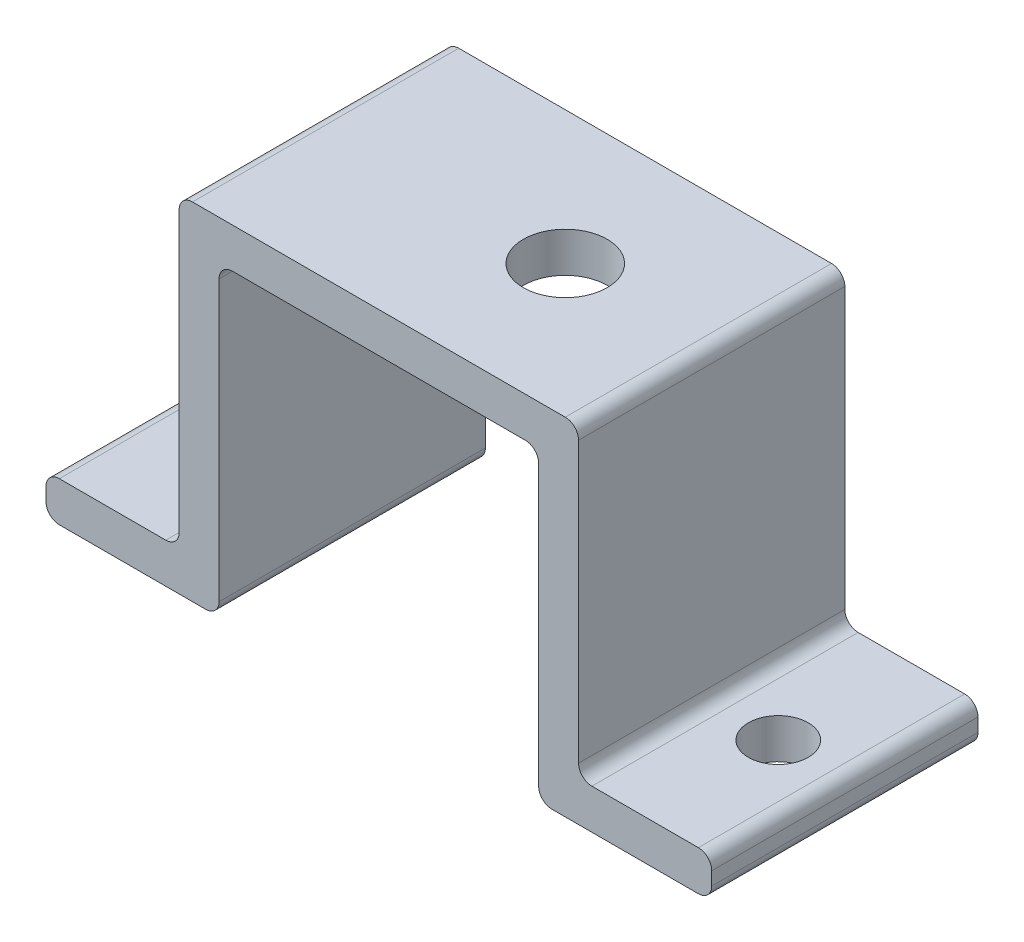
SolidWorks part; units mm, degrees
ref_plane "Front Plane" through (0, 0, 0) normal (0, 0, 1) x (1, 0, 0)
ref_plane "Top Plane" through (0, 0, 0) normal (0, 1, 0) x (1, 0, 0)
ref_plane "Right Plane" through (0, 0, 0) normal (1, 0, 0) x (0, 0, -1)
sketch "Sketch2" plane through (0, 0, 0) normal (0, 0, 1) x (1, 0, 0)
  line L1 (-12, 0) -> (12, 0)
  line L2 (-15, -20) -> (-15, 3)
  line L3 (-15, 3) -> (15, 3)
  line L4 (15, -20) -> (15, 3)
  line L15 (-15, -20) -> (-25, -20)
  line L16 (-12, 0) -> (-12, -23)
  line L17 (-12, -23) -> (-25, -23)
  line L18 (-25, -20) -> (-25, -23)
  line L19 (15, -20) -> (25, -20)
  line L20 (12, 0) -> (12, -23)
  line L21 (12, -23) -> (25, -23)
  line L22 (25, -20) -> (25, -23)
  point P0 (0, 0)
  point P7 (-20, -6.3216)
  point P8 (-27.8471, 12.8275)
  point P10 (-35, -6.8038)
  point P11 (-24.2653, -8.6636)
  point P18 (-86.5056, -58.0001)
  point P19 (0, 0)
  point P20 (-61.8668, 28.3256)
  point P21 (20, -8.2503)
  point P22 (-20, -8.6636)
  point P23 (-12, -11.5)
  point P24 (-25.023, -13.692)
  point P25 (0, 0)
  point P26 (0, 0)
  point P27 (-35, -15.1385)
  point P28 (-29, 3)
  point P29 (-29, -11.6255)
  point P30 (35, -15.9651)
  dimension "D1" = 50
  dimension "D2" = 24
  dimension "D3" = 3
  dimension "D4" = 3
  dimension "D5" = 3
  dimension "D6" = 23
extrude "Boss-Extrude1" add sketch "Sketch2" along normal blind 20
sketch "Sketch3" plane through (0, 3, 0) normal (0, 1, 0) x (1, 0, 0)
  line L0 (-15, -10) -> (15, -10) construction
  line L1 (-15, -20) -> (-15, 0) construction
  line L2 (15, -20) -> (15, 0) construction
  line L3 (15, -20) -> (15, 0) construction
  circle A0 centre (4, -10) radius 3.15
  point P10 (-0.4763, -13.1302)
  point P11 (-14.494, -10)
  point P12 (12.3165, -10)
  dimension "D1" = 6.3
  dimension "D2" = 11
extrude "Cut-Extrude1" cut sketch "Sketch3" against normal through all
sketch "Sketch5" plane through (0, -20, 0) normal (0, 1, 0) x (1, 0, 0)
  line L0 (-20, -10) -> (20, -10) construction
  line L3 (0, 0) -> (0, -20) construction
  line L6 (15, 0) -> (-15, 0) construction
  line L7 (15, -20) -> (-15, -20) construction
  circle A0 centre (-20, -10) radius 2.25
  circle A1 centre (20, -10) radius 2.25
  point P2 (0, -10)
  point P7 (0, 0)
  dimension "D1" = 4.5
  dimension "D2" = 40
extrude "Cut-Extrude2" cut sketch "Sketch5" against normal through all
fillet "Fillet1" radius 1 12 edges at (25, -20, 10) (-25, -23, 10) (25, -23, 10) (-25, -20, 10) (-15, -20, 10) (-15, 3, 10) (15, 3, 10) (15, -20, 10) (12, -23, 10) (-12, -23, 10) (-12, 0, 10) (12, 0, 10)
